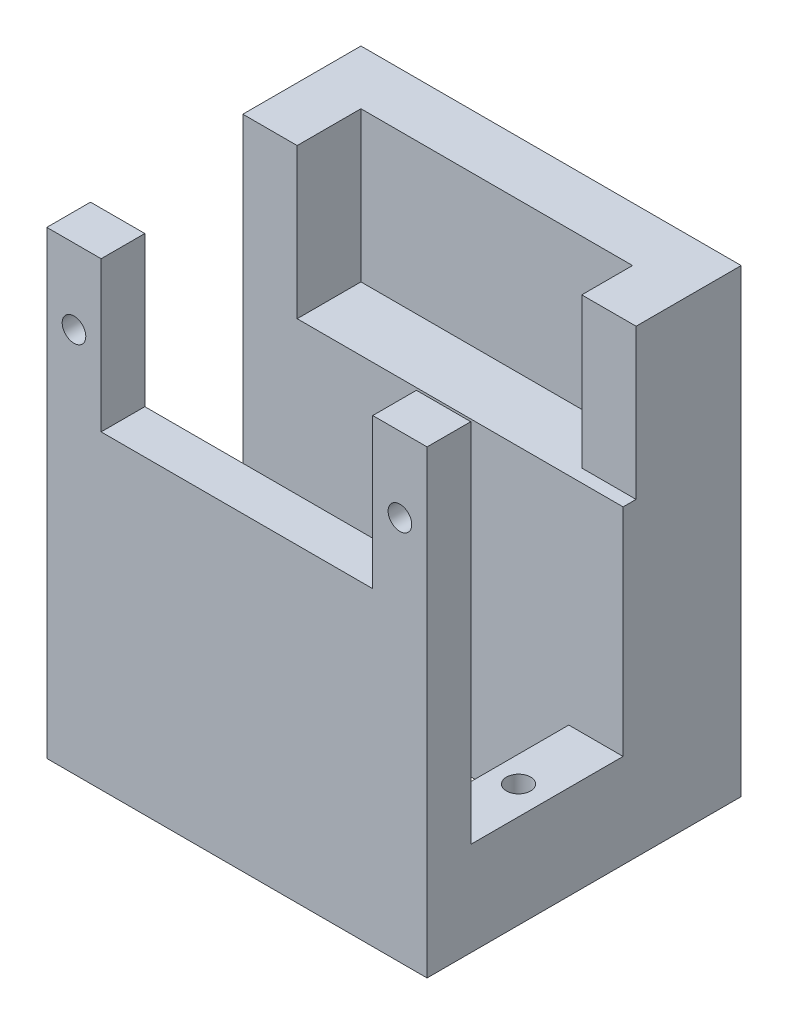
SolidWorks part; units mm, degrees
ref_plane "Front" through (0, 0, 0) normal (0, 0, 1) x (1, 0, 0)
ref_plane "Top" through (0, 0, 0) normal (0, 1, 0) x (1, 0, 0)
ref_plane "Right" through (0, 0, 0) normal (1, 0, 0) x (0, 0, -1)
sketch "Sketch1" plane through (0, 0, 0) normal (0, 1, 0) x (1, 0, 0)
  line L0 (-16.55, 6.45) -> (6.45, 6.45)
  line L1 (-16.55, 6.45) -> (-16.55, -6.45)
  line L2 (6.45, 6.45) -> (6.45, -6.45)
  line L3 (-16.55, -6.45) -> (6.45, -6.45)
  line L4 (-21.15, 16.45) -> (11.05, 16.45)
  line L5 (-21.15, 16.45) -> (-21.15, -10.15)
  line L6 (11.05, 16.45) -> (11.05, -10.15)
  line L7 (-21.15, -10.15) -> (11.05, -10.15)
  line L8 (-16.55, 6.45) -> (-9.05, 6.45)
  line L9 (-16.55, 6.45) -> (-16.55, -6.45)
  line L10 (-9.05, 6.45) -> (-9.05, -6.45)
  line L11 (-16.55, -6.45) -> (-9.05, -6.45)
  circle A1 centre (0, 0) radius 6.45
  dimension "D1" = 12.9
  dimension "D2" = 23
  dimension "D3" = 3.7
  dimension "D4" = 10
  dimension "D5" = 4.6
  dimension "D6" = 7.5
  dimension "D7" = 4.6
extrude "Boss-Extrude1" add sketch "Sketch1" against normal blind 4.25 contours L5 L7 L6 L4 L3 L1 L0 L2 | L10 L0 L1 L3 region at (-12.8, 0, 0) region at (-5.05, 0, -16.0323)
extrude "Boss-Extrude2" add sketch "Sketch1<3>" along normal blind 3.7 contours L5 L7 L6 L4 L3 L1 L0 L2 region at (-5.05, 0, -16.0323)
sketch "Sketch1<3>" plane through (0, 0, 0) normal (0, 1, 0) x (1, 0, 0) same geometry as "Sketch1"
sketch "Sketch2" plane through (0, 3.7, 0) normal (0, 1, 0) x (1, 0, 0)
  circle A4 centre (-18.75, 0) radius 1.025
  circle A5 centre (-18.75, 0) radius 1.025
  circle A7 centre (8.65, 0) radius 1.025
  circle A8 centre (8.65, 0) radius 1.025
  point P17 (-18.85, 0)
  dimension "D1" = 0.1
  dimension "D2" = 0.1
extrude "Cut-Extrude1" cut sketch "Sketch2" against normal blind 5 contours A5 | A8
sketch "Sketch3" plane through (0, 3.7, 0) normal (0, 1, 0) x (1, 0, 0)
  line L12 (-21.15, -6.45) -> (11.05, -6.45)
  line L13 (-21.15, -6.45) -> (-21.15, -10.15)
  line L14 (11.05, -6.45) -> (11.05, -10.15)
  line L15 (-21.15, -10.15) -> (11.05, -10.15)
  line L16 (-21.15, 16.45) -> (-21.15, -10.15) construction
  line L17 (11.05, 16.45) -> (11.05, -10.15) construction
  line L18 (-16.55, -6.45) -> (6.45, -6.45) construction
  line L19 (-16.55, 6.45) -> (6.45, 6.45) construction
  line L20 (-21.15, 16.45) -> (11.05, 16.45)
  line L21 (-21.15, 16.45) -> (-21.15, 6.45)
  line L22 (-21.15, 6.45) -> (11.05, 6.45)
  line L23 (11.05, 16.45) -> (11.05, 6.45)
extrude "Boss-Extrude3" add sketch "Sketch3" along normal blind 18.3
sketch "Sketch4" plane through (0, 22, 0) normal (0, 1, 0) x (1, 0, 0)
  line L0 (-21.15, 6.45) -> (11.05, 6.45) construction
  line L1 (-21.15, 16.45) -> (-16.55, 16.45)
  line L2 (-21.15, 16.45) -> (-21.15, 6.45)
  line L3 (-21.15, 6.45) -> (-16.55, 6.45)
  line L4 (-16.55, 11.85) -> (-16.55, 6.45)
  line L5 (-16.55, 11.85) -> (-16.55, 16.45) construction
  line L6 (11.05, 16.45) -> (6.45, 16.45)
  line L7 (11.05, 16.45) -> (11.05, 7.55)
  line L8 (11.05, 7.55) -> (6.45, 7.55)
  line L9 (6.45, 11.85) -> (6.45, 7.55)
  line L10 (11.05, -6.45) -> (-21.15, -6.45) construction
  line L11 (6.45, 11.85) -> (6.45, 16.45) construction
  line L16 (11.05, 16.45) -> (-21.15, 16.45) construction
  line L21 (-16.55, 16.45) -> (6.45, 16.45)
  line L23 (-16.55, 11.85) -> (6.45, 11.85)
  line L26 (-21.15, -10.15) -> (-16.55, -10.15)
  line L27 (-21.15, -10.15) -> (-21.15, -6.45)
  line L28 (-21.15, -6.45) -> (-16.55, -6.45)
  line L29 (-16.55, -10.15) -> (-16.55, -6.45)
  line L30 (11.05, -10.15) -> (6.45, -10.15)
  line L31 (11.05, -10.15) -> (11.05, -6.45)
  line L32 (11.05, -6.45) -> (6.45, -6.45)
  line L33 (6.45, -10.15) -> (6.45, -6.45)
  dimension "D1" = 4.6
  dimension "D2" = 4.6
  dimension "D3" = 14
  dimension "D4" = 18.3
extrude "Boss-Extrude4" add sketch "Sketch4" along normal blind 12.7
sketch "Sketch5" plane through (0, 0, 10.15) normal (0, 0, 1) x (1, 0, 0)
  line L0 (-16.55, 28.35) -> (-21.15, 28.35) construction
  line L1 (-16.55, 34.7) -> (-16.55, 22) construction
  line L2 (-21.15, -4.25) -> (-21.15, 34.7) construction
  line L3 (6.45, 28.35) -> (11.05, 28.35) construction
  line L4 (6.45, 34.7) -> (6.45, 22) construction
  line L5 (11.05, -4.25) -> (11.05, 34.7) construction
  circle A0 centre (-18.85, 28.35) radius 1
  circle A1 centre (8.75, 28.35) radius 1
  dimension "D1" = 2
  dimension "D2" = 2
extrude "Cut-Extrude2" cut sketch "Sketch5" against normal up to next
